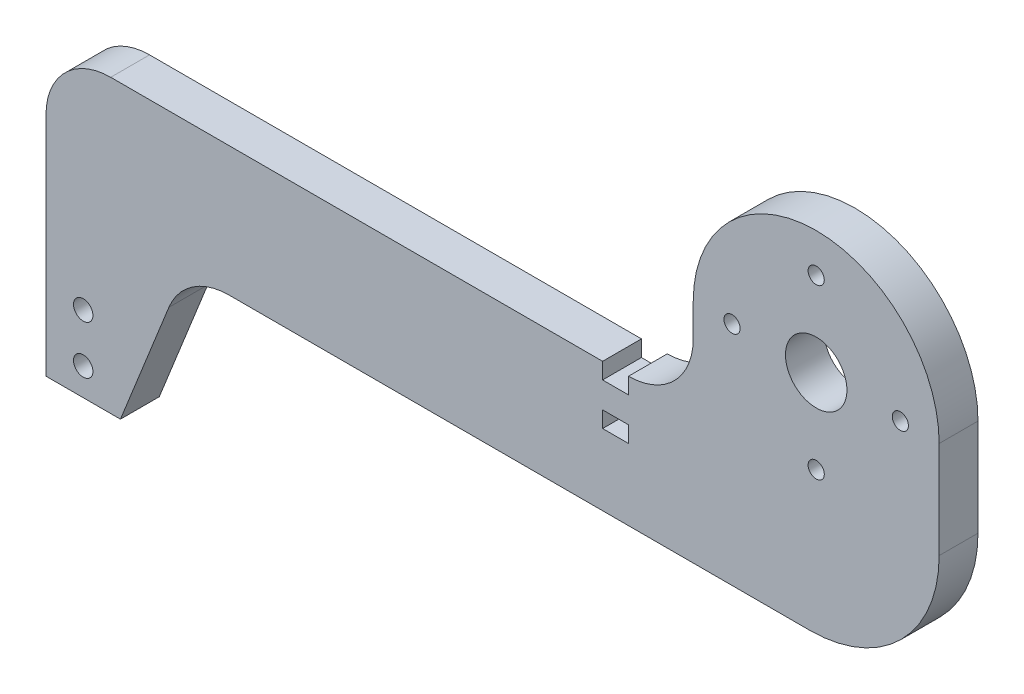
SolidWorks part; units mm, degrees
ref_plane "Спереди" through (0, 0, 0) normal (0, 0, 1) x (1, 0, 0)
ref_plane "Сверху" through (0, 0, 0) normal (0, 1, 0) x (1, 0, 0)
ref_plane "Справа" through (0, 0, 0) normal (1, 0, 0) x (0, 0, -1)
sketch "Эскиз1" plane through (0, 0, 0) normal (0, 0, 1) x (1, 0, 0)
  line L0 (-19, 0) -> (-19, -35)
  line L1 (-19, -35) -> (19, -35)
  line L2 (19, -35) -> (19, 0)
  line L3 (-113.25, -48.25) -> (-113.25, -55.75) construction
  line L4 (19, -35) -> (-119, -35)
  line L5 (19, -35) -> (19, -15)
  line L6 (19, -15) -> (-119, -15)
  line L7 (-119, -35) -> (-119, -15)
  line L8 (-107.5, -35) -> (-119, -35)
  line L9 (-107.5, -35) -> (-107.5, -60)
  line L10 (-107.5, -60) -> (-119, -60)
  line L11 (-119, -35) -> (-119, -60)
  line L12 (-107.5, -60) -> (-97.5, -35)
  line L14 (-33, -15) -> (-29, -15)
  line L15 (-33, -15) -> (-33, -17.5)
  line L16 (-33, -17.5) -> (-29, -17.5)
  line L17 (-29, -15) -> (-29, -17.5)
  line L18 (-33, -21.5) -> (-29, -21.5)
  line L19 (-33, -21.5) -> (-33, -24)
  line L20 (-33, -24) -> (-29, -24)
  line L21 (-29, -21.5) -> (-29, -24)
  circle A0 centre (0, 0) radius 19
  circle A1 centre (0, 0) radius 4.75
  circle A2 centre (0, 13) radius 1.25
  circle A3 centre (13, 0) radius 1.25
  circle A4 centre (0, -13) radius 1.25
  circle A5 centre (-13, 0) radius 1.25
  circle A8 centre (-113.25, -48.25) radius 1.5
  circle A9 centre (-113.25, -55.75) radius 1.5
  point P15 (0, 0)
  point P35 (-113.25, -35)
  dimension "D1" = 38
  dimension "D2" = 9.5
  dimension "D3" = 2.5
  dimension "D9" = 4
  dimension "D14" = 3
  dimension "D4" = 13
  dimension "D6" = 35
  dimension "D7" = 20
  dimension "D8" = 100
  dimension "D10" = 4
  dimension "D11" = 10
  dimension "D12" = 11.5
  dimension "D13" = 7.5
  dimension "D15" = 33.25
  dimension "D16" = 4.25
  dimension "D17" = 10
  dimension "D18" = 2.5
  dimension "D5" = 4
extrude "Бобышка-Вытянуть1" add sketch "Эскиз1" along normal blind 6 contours A0 L0 L6 | A0 L6 L2 | A0 L6 L0 L1 L2 | L6 L17 L16 L15 L7 L4 L0 L18 L21 L20 L19 | L9 L12 L4 | L4 L11 L10 L9 A8 A9 | A0 L6 A5 A4 A3 A2 A1 | L6 A0 region at (-16.8972, -11.4102, 0) region at (0, 18.4901, 0) region at (0, -25.7662, 0) region at (-69.3838, -25.0556, 0) region at (16.8972, -11.4102, 0) region at (0, -16.6154, 0) region at (-104.1667, -43.3333, 0) region at (-107.7752, -47.5, 0)
fillet "Скругление1" radius 10 1 edges at (-19, -15, 3)
fillet "Скругление2" radius 20 1 edges at (19, -35, 3)
fillet "Скругление3" radius 10 2 edges at (-119, -15, 3) (-97.5, -35, 3)
